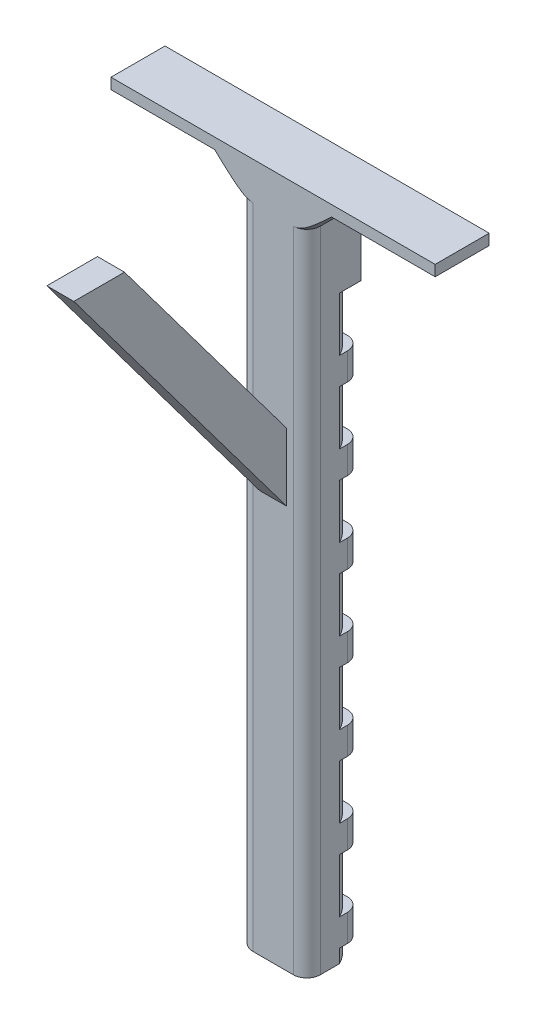
SolidWorks part; units mm, degrees
ref_plane "Front Plane" through (0, 0, 0) normal (0, 0, 1) x (1, 0, 0)
ref_plane "Top Plane" through (0, 0, 0) normal (0, 1, 0) x (1, 0, 0)
ref_plane "Right Plane" through (0, 0, 0) normal (1, 0, 0) x (0, 0, -1)
sketch "Sketch1" plane through (0, 0, 0) normal (0, 0, 1) x (1, 0, 0)
  line L1 (-12.5, 125) -> (12.5, 125)
  line L2 (-12.5, 125) -> (-12.5, -125)
  line L3 (-12.5, -125) -> (12.5, -125)
  line L4 (12.5, 125) -> (12.5, -125)
  line L5 (-12.5, 125) -> (12.5, -125) construction
  line L6 (-12.5, -125) -> (12.5, 125) construction
  point P0 (0, 0)
  dimension "D1" = 25
  dimension "D2" = 250
extrude "Boss-Extrude1" add sketch "Sketch1" along normal blind 20
sketch "Sketch2" plane through (0, 0, 0) normal (0, 0, 1) x (1, 0, 0)
  line L0 (12.5, 125) -> (-12.5, 125) construction
  line L1 (-60, 129) -> (60, 129)
  line L2 (-60, 129) -> (-60, 125)
  line L3 (-60, 125) -> (60, 125)
  line L4 (60, 129) -> (60, 125)
  line L5 (-60, 129) -> (60, 125) construction
  line L6 (-60, 125) -> (60, 129) construction
  line L7 (0, 127) -> (0, 0) construction
  point P0 (0, 127)
  dimension "D1" = 4
  dimension "D2" = 120
extrude "Boss-Extrude2" add sketch "Sketch2" along normal blind 20
sketch "Sketch5" plane through (0, 0, 0) normal (0, 1, 0) x (1, 0, 0)
  line L0 (12.5, -8) -> (-12.5, -8) construction
  line L1 (1.1995, -0.0524) -> (1.1995, 0)
  line L2 (-1.1995, -0.0524) -> (-1.1995, 0)
  line L3 (-1.1995, -0.0524) -> (1.1995, -0.0524) construction
  line L4 (12.5, 0) -> (-12.5, 0)
  line L5 (12.5, -20) -> (12.5, 0)
  line L6 (-12.5, -20) -> (12.5, -20)
  line L7 (-12.5, 0) -> (-12.5, -20)
  line L8 (12.5, 0) -> (1.1995, 0)
  line L9 (12.5, -8) -> (12.5, 0)
  line L11 (-12.5, 0) -> (-12.5, -8)
  line L12 (-1.1995, 0) -> (-12.5, 0)
  arc A0 (12.5, -8) -> (1.1995, -0.0524) centre (0, -13.7656) ccw
  arc A1 (-1.1995, -0.0524) -> (-12.5, -8) centre (0, -13.7656) ccw
  point P11 (-1.6212, -0.0708)
  dimension "D2" = 8
  dimension "D1" = 0
extrude "Cut-Extrude1" cut sketch "Sketch5" against normal blind 20
pattern_linear "LPattern1" count 5 spacing 30 along (0, -1, 0) count 4 spacing 30 along (0, 1, 0) of "Cut-Extrude1"
fillet "Fillet1" radius 5 14 edges at (-12.5, 65, 0) (12.5, 65, 0) (12.5, 35, 0) (12.5, 5, 0) (12.5, -25, 0) (12.5, -55, 0) (12.5, -85, 0) (12.5, -115, 0) (-12.5, 35, 0) (-12.5, 5, 0) (-12.5, -25, 0) (-12.5, -55, 0) (-12.5, -85, 0) (-12.5, -115, 0)
sketch "Sketch6" plane through (0, 0, 0) normal (1, 0, 0) x (0, 0, -1)
  line L0 (-20, 49) -> (-80, 129)
  line L1 (-20, -125) -> (-20, 125) construction
  line L2 (-80, 129) -> (-20, 129) construction
  line L3 (-20, 24) -> (-98.75, 129)
  line L4 (-98.75, 129) -> (-80, 129)
  line L5 (-20, 49) -> (-20, 24)
  dimension "D1" = 60
  dimension "D2" = 80
  dimension "D3" = 15
extrude "Boss-Extrude4" add sketch "Sketch6" along normal blind 5 and the other way blind 5
fillet "Fillet2" radius 5 2 edges at (12.5, 0, 20) (-12.5, 0, 20)
chamfer "Chamfer1" distance 10 angle 45 4 edges at (11.0355, 125, 18.5355) (12.5, 125, 7.5) (-11.0355, 125, 18.5355) (-12.5, 125, 7.5)
